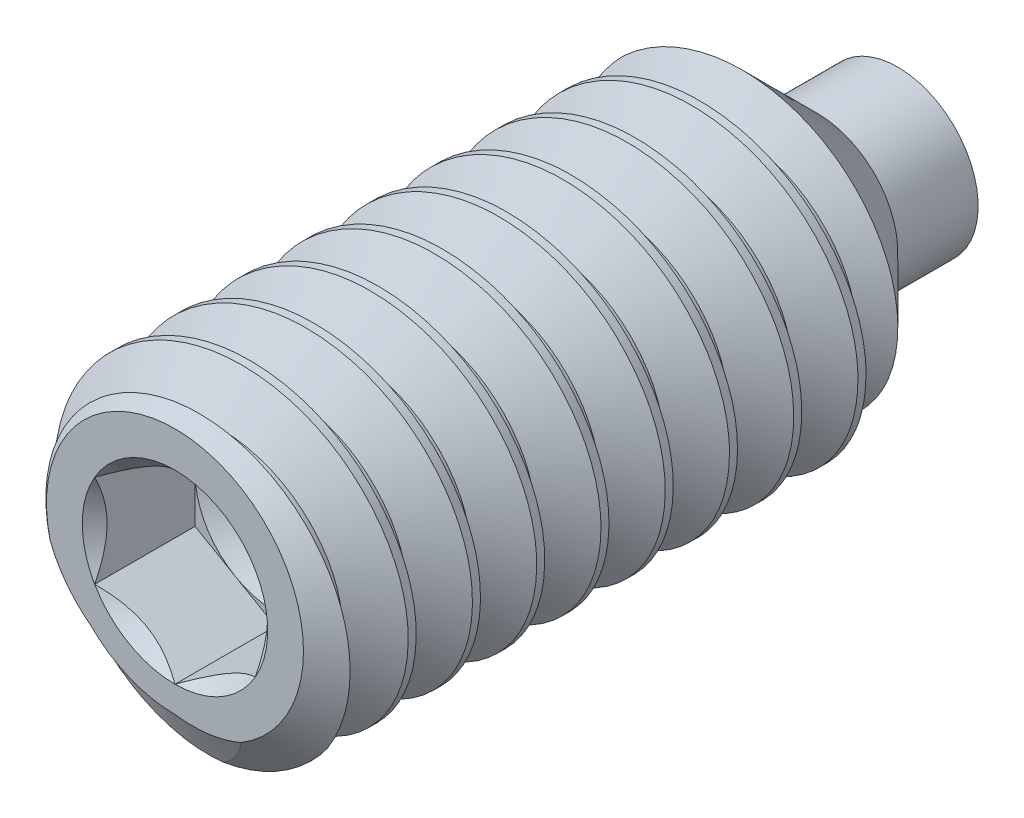
SolidWorks part; units mm, degrees
ref_plane "Front" through (0, 0, 0) normal (0, 0, 1) x (1, 0, 0)
ref_plane "Top" through (0, 0, 0) normal (0, 1, 0) x (1, 0, 0)
ref_plane "Right" through (0, 0, 0) normal (1, 0, 0) x (0, 0, -1)
sketch "Sketch22" plane through (0, 0, 0) normal (1, 0, 0) x (0, 0, -1)
  line L0 (-7.1438, 0) -> (-7.1438, 2.54)
  line L1 (-7.1438, 2.54) -> (-6.6991, 3.175)
  line L2 (-6.6991, 3.175) -> (3.9688, 3.175)
  line L3 (3.9688, 3.175) -> (5.5563, 1.5875)
  line L4 (-7.1438, 2.54) -> (-7.1438, -2.54) construction
  line L5 (7.1438, 0) -> (-7.1438, 0)
  line L6 (0, 3.175) -> (0, -3.175) construction
  line L8 (5.5563, 1.5875) -> (7.1438, 1.5875)
  line L9 (-5.3339, -3.175) -> (5.3339, -3.175) construction
  line L10 (7.1438, 1.5875) -> (7.1438, 0)
  line L11 (7.1438, 1.5875) -> (7.1438, -1.5875) construction
  dimension "D1" = 45
  dimension "Dia" = 6.35
  dimension "D2" = 5.08
  dimension "Length" = 12.7
  dimension "D3" = 35
  dimension "A" = 3.175
  dimension "B" = 1.5875
revolve "Revolve1" add sketch "Sketch22" angle 360 about L5
ref_plane "Plane1" through (0, 0, -5.5563) normal (0, 0, 1) x (1, 0, 0)
sketch "Sketch27" plane through (0, 0, -5.5563) normal (0, 0, 1) x (1, 0, 0)
  circle A0 centre (0, 0) radius 3.175 construction
  circle A1 centre (0, 0) radius 3.175
curve "Helix/Spiral1" pitch 1.27 height 15.24 radius 3.175 centre (0, 0, -5.5563) axis (0, 0, 1) start towards (0, 1, 0)
sketch "Sketch28" plane through (0, 0, 0) normal (1, 0, 0) x (0, 0, -1)
  line L0 (5.5563, 3.175) -> (6.6675, 3.175)
  line L1 (6.6675, 3.175) -> (6.1913, 2.3501)
  line L2 (6.1913, 2.3501) -> (6.0325, 2.3501)
  line L3 (6.0325, 2.3501) -> (5.5563, 3.175)
  line L4 (5.7944, 2.7626) -> (6.4294, 2.7626) construction
  line L6 (-6.6991, 3.175) -> (3.9688, 3.175) construction
  line L7 (5.5563, 3.4925) -> (5.5563, -3.4925) construction
  dimension "D1" = 0.1588
  dimension "D2" = 0.635
  dimension "D3" = 60
sweep "Cut-Sweep2" cut profiles "Sketch28" path "Helix/Spiral1"
sketch "Sketch23" plane through (0, 0, 7.1438) normal (0, 0, 1) x (1, 0, 0)
  line L1 (0, 1.8331) -> (-1.5875, 0.9165)
  line L2 (-1.5875, 0.9165) -> (-1.5875, -0.9165)
  line L3 (-1.5875, -0.9165) -> (0, -1.8331)
  line L4 (0, -1.8331) -> (1.5875, -0.9165)
  line L5 (1.5875, -0.9165) -> (1.5875, 0.9165)
  line L6 (1.5875, 0.9165) -> (0, 1.8331)
  circle A0 centre (0, 0) radius 1.5875 construction
  dimension "Hex" = 3.175
extrude "Cut-Extrude10" cut sketch "Sketch23" against normal blind 1.9844
sketch "Sketch24" plane through (0, 0, 7.1438) normal (0, 0, 1) x (1, 0, 0)
  circle A0 centre (0, 0) radius 1.8331
extrude "Cut-Extrude11" cut sketch "Sketch24" against normal through all draft 45
sketch "Sketch26" plane through (0, 0, 5.1594) normal (0, 0, 1) x (1, 0, 0)
  circle A0 centre (0, 0) radius 1.5875 construction
  circle A1 centre (0, 0) radius 1.5875
extrude "Cut-Extrude12" cut sketch "Sketch26" against normal through all draft 60
sketch "Sketch30" plane through (0, 0, 0) normal (1, 0, 0) x (0, 0, -1)
  line L0 (-6.6991, 3.175) -> (3.9688, 3.175) construction
  line L1 (-7.1438, 0) -> (-7.1438, 2.54) construction
  line L2 (5.5563, 3.175) -> (5.5563, -3.175) construction
  line L3 (-5.3339, -3.175) -> (5.3339, -3.175) construction
  point P0 (-7.1438, 3.175)
  point P1 (7.1438, 3.175)
  point P2 (7.1438, -3.175)
  point P11 (1.1113, -3.175)
  dimension "D1" = 4.445
equation "\"D1@Sketch28\" = \"D4@Helix/Spiral1\" * .125"
equation "\"D3@Helix/Spiral1\" = \"Length@Sketch22\" +  ( \"D4@Helix/Spiral1\" * 2 ) "
equation "\"D1@Sketch30\" = \"D4@Helix/Spiral1\" * 3.5"
equation "\"hex Depth@Cut-Extrude10\" = \"Hex@Sketch23\" * .625"
equation "\"D2@Sketch28\" = \"D4@Helix/Spiral1\" * .5"
equation "\"D2@Sketch22\" = \"Dia@Sketch22\" * .8"
